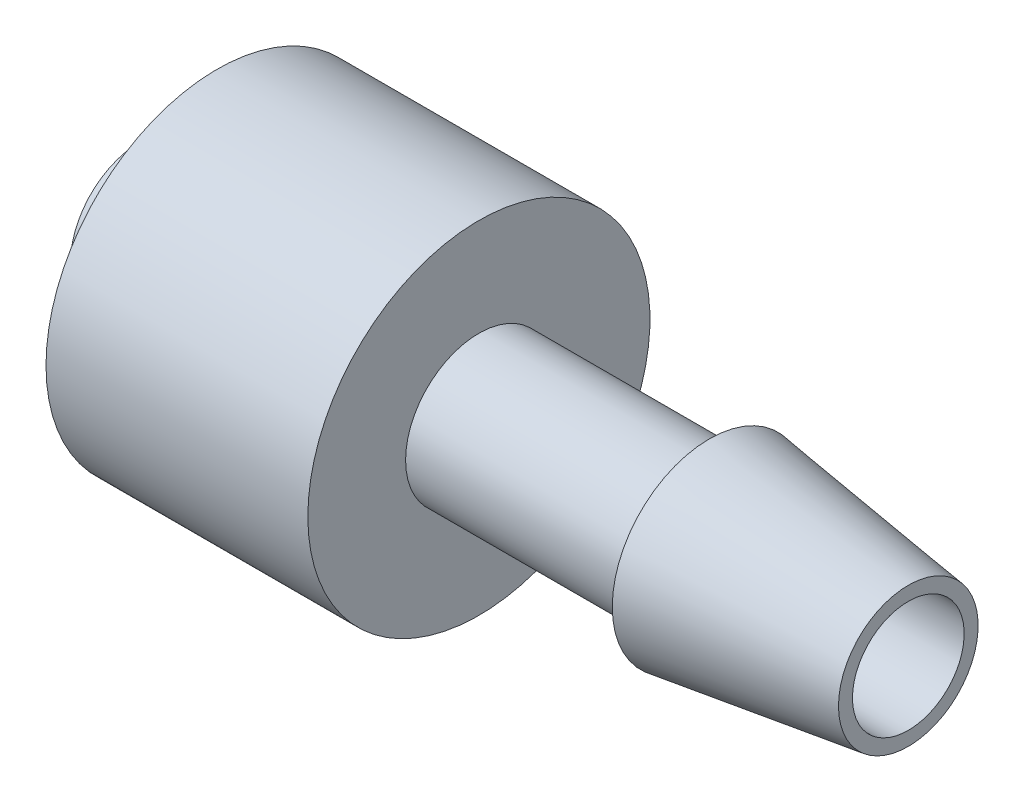
SolidWorks part; units mm, degrees
ref_plane "Płaszczyzna przednia" through (0, 0, 0) normal (0, 0, 1) x (1, 0, 0)
ref_plane "Płaszczyzna górna" through (0, 0, 0) normal (0, 1, 0) x (1, 0, 0)
ref_plane "Płaszczyzna prawa" through (0, 0, 0) normal (1, 0, 0) x (0, 0, -1)
sketch "Sketch1" plane through (0, 0, 0) normal (0, 0, 1) x (1, 0, 0)
  line L1 (0.4386, 0.4) -> (-5.2614, 1.18)
  line L2 (-5.2614, 1.18) -> (-5.2614, 0.5)
  line L3 (-5.2614, 0.5) -> (-11.8614, 0.5)
  line L4 (-11.8614, 0.5) -> (-11.8614, 3.3)
  line L5 (-11.8614, 3.3) -> (-19.3614, 3.3)
  line L6 (-19.3614, 3.3) -> (-19.3614, 2.4)
  line L7 (-12.9614, 2.4) -> (-19.3614, 2.4)
  line L9 (0.4386, 0.4) -> (0.4386, 0)
  line L11 (-11.8614, 0) -> (0.4386, 0)
  line L13 (-11.8614, 0) -> (-11.8614, -0.1)
  line L16 (-11.8614, -0.1) -> (-21.5614, -0.1)
  line L17 (-21.5614, -0.1) -> (-21.5614, 0.4)
  line L18 (-21.5614, 0.4) -> (-12.9614, 0.4)
  line L19 (-12.9614, 0.4) -> (-12.9614, 2.4)
  line L20 (-25.5815, -1.6) -> (5.5906, -1.6)
  point P12 (-5.2333, 0.7409)
  dimension "D1" = 0.4
  dimension "D2" = 5.7
  dimension "D3" = 12.3
  dimension "D4" = 6.6
  dimension "D5" = 7.5
  dimension "D6" = 9.7
  dimension "D7" = 1.5
  dimension "D8" = 2
  dimension "6,4" = 6.4
  dimension "D9" = 4
  dimension "D10" = 1.6
  dimension "D11" = 2.78
  dimension "D12" = 0.5
  dimension "D13" = 4.9
ref_axis "Axis1" through (-25.67, -1.6, 0) along (1, 0, 0)
revolve "Revolve2" add sketch "Sketch1" angle 360 about L20 region at (0.216, 0.2, 0)
